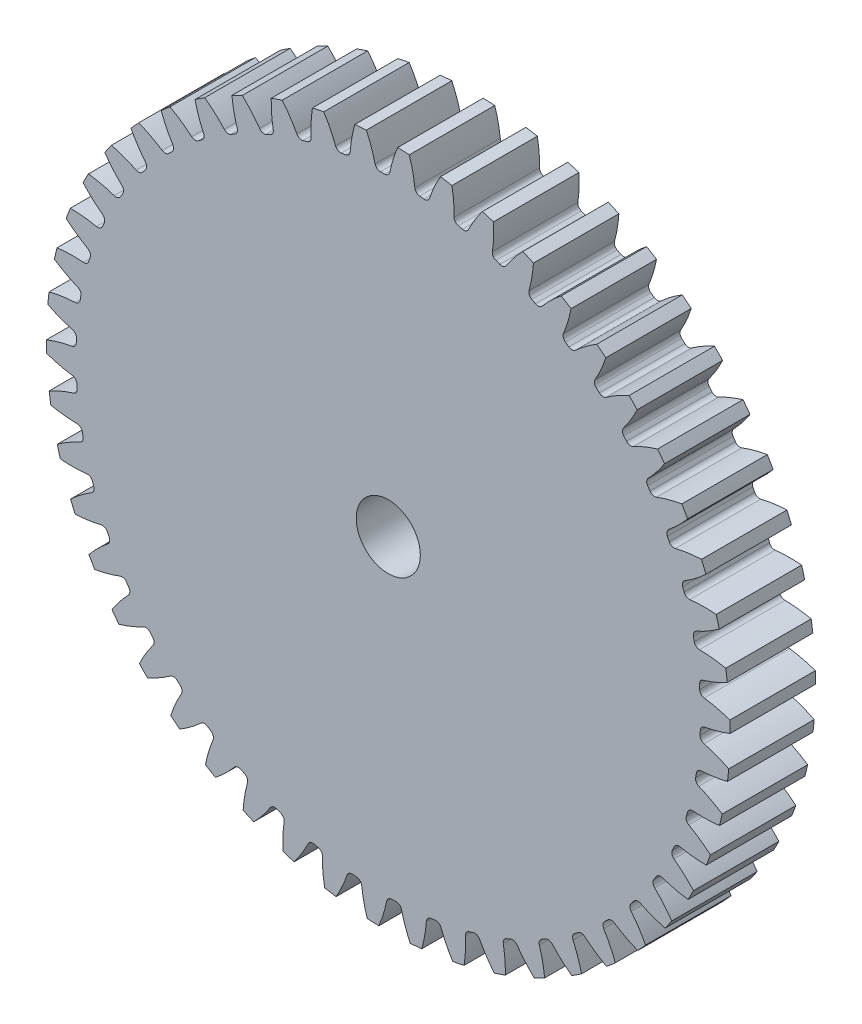
SolidWorks part; units mm, degrees
ref_plane "Front" through (0, 0, 0) normal (0, 0, 1) x (1, 0, 0)
ref_plane "Top" through (0, 0, 0) normal (0, 1, 0) x (1, 0, 0)
ref_plane "Right" through (0, 0, 0) normal (1, 0, 0) x (0, 0, -1)
sketch "Sketch3" plane through (0, 0, 0) normal (0, 0, 1) x (1, 0, 0)
  circle A0 centre (0, 0) radius 25.4
  dimension "od" = 50.8
extrude "gearBody" add sketch "Sketch3" along normal blind 6.35
sketch "Sketch2" plane through (0, 0, 0) normal (0, 0, 1) x (1, 0, 0)
  line L0 (0, 0) -> (21.8453, 9.0486) construction
  line L1 (29.4137, -6.2294) -> (0, 0) construction
  line L2 (0, 0) -> (36.3143, 0) construction
  line L3 (24.4213, -0.2936) -> (24.3506, -1.8801) construction
  line L5 (24.386, -1.0869) -> (0, 0) construction
  line L7 (0, 0) -> (23.6451, 0) construction
  arc A0 (23.6404, -0.4745) -> (23.5889, -1.6304) centre (0, 0) ccw construction
  arc A1 (25.4, 0.0332) -> (25.2963, -2.2927) centre (0, 0) ccw construction
  arc A2 (24.4213, -0.2936) -> (24.3506, -1.8801) centre (0, 0) ccw construction
  arc A3 (23.1693, -1.1922) -> (23.1835, -0.8737) centre (0, 0) ccw
  arc A4 (29.4137, -6.2294) -> (23.4627, -1.5957) centre (20.9537, -10.9561) ccw
  arc A5 (29.4137, -6.2294) -> (29.8512, 3.5881) centre (0, 0) ccw
  arc A6 (29.8512, 3.5881) -> (23.5117, -0.4979) centre (21.8453, 9.0486) cw
  arc A7 (23.1835, -0.8737) -> (23.5117, -0.4979) centre (23.5799, -0.8886) cw
  arc A8 (23.4627, -1.5957) -> (23.1693, -1.1922) centre (23.5654, -1.2126) cw
  point P6 (29.8512, 3.5881)
  point P22 (29.4137, -6.2294)
  dimension "baseDia" = 47.2903
  dimension "od" = 50.8
  dimension "pd" = 48.8462
  dimension "rd" = 46.3999
  dimension "rFillet" = 0.3966
  dimension "pointX" = 29.8512
  dimension "pointY" = 3.5881
  dimension "CTT" = 1.5865
  dimension "flankCenterAngle" = 22.5
extrude "toothCut" cut sketch "Sketch2" along normal through all
pattern_circular "CirPattern1" count 50 over 360 about axis through (0, 0, 6.35) along (0, 0, -1) of "toothCut"
ref_axis "toothSpace" through (0, 0, 0) along (0.999, -0.0445, 0)
ref_axis "Axis2" through (25.2537, -2.722, 0) along (-0.9942, 0.1072, 0)
sketch "hub1Dia" plane through (0, 0, 0) normal (0, 0, -1) x (-1, 0, 0)
  circle A0 centre (0, 0) radius 12.7
  dimension "hub1Dia" = 25.4
sketch "hub2Dia" plane through (0, 0, 6.35) normal (0, 0, 1) x (1, 0, 0)
  circle A0 centre (0, 0) radius 12.7
  dimension "hub2dia" = 25.4
sketch "boreDia" plane through (0, 0, 0) normal (0, 0, 1) x (1, 0, 0)
  circle A0 centre (0, 0) radius 2.3812
  dimension "boreDia" = 4.7625
extrude "bore" cut sketch "boreDia" against normal mid plane 25400
sketch "kwy1sketch" plane through (0, 0, 0) normal (0, 0, 1) x (1, 0, 0)
  line L0 (-6.033, 0.5227) -> (0, 0) construction
  line L1 (28.7738, 10.2545) -> (26.5813, -15.0507)
  line L2 (26.5813, -15.0507) -> (-5.0502, -12.31)
  line L3 (28.7738, 10.2545) -> (-2.8577, 12.9952)
  line L4 (-5.0502, -12.31) -> (0, 0)
  line L5 (0, 0) -> (-2.8577, 12.9952)
  line L6 (0, 0) -> (23.177, -1.033) construction
  line L7 (27.6776, -2.3981) -> (0, 0) construction
  arc A7 (23.1693, -1.1922) -> (23.1835, -0.8737) centre (0, 0) ccw construction
  point P9 (27.6776, -2.3981)
  point P13 (-1.0064, 0.0872)
  dimension "kwy1width" = 25.4
  dimension "kwy1depth" = 27.7812
  dimension "kwy1angle" = 2.4
  dimension "kwy1Depth2" = 31.75
sketch "kwy2sketch" plane through (0, 0, 0) normal (0, 0, 1) x (1, 0, 0)
  line L0 (23.177, -1.033) -> (0, 0) construction
  line L1 (0, 0) -> (-3.2033, -2.6925) construction
  line L2 (13.0951, 27.5972) -> (29.4382, 8.1534)
  line L3 (29.4382, 8.1534) -> (5.1335, -12.2755)
  line L4 (13.0951, 27.5972) -> (-11.2097, 7.1683)
  line L5 (5.1335, -12.2755) -> (0, 0)
  line L6 (0, 0) -> (-11.2097, 7.1683)
  arc A2 (23.1693, -1.1922) -> (23.1835, -0.8737) centre (0, 0) ccw construction
  point P10 (21.2667, 17.8753)
  dimension "kwy2angle" = 42.6
  dimension "kwy2Width" = 25.4
  dimension "kwy2depth" = 27.7812
  dimension "kwy2Depth2" = 31.75
sketch "kwy3sketch" plane through (0, 0, 0) normal (0, 0, 1) x (1, 0, 0)
  line L0 (23.177, -1.033) -> (0, 0) construction
  line L1 (0, 0) -> (-0.2613, -3.0161) construction
  line L2 (-10.2545, 28.7738) -> (15.0507, 26.5813)
  line L3 (15.0507, 26.5813) -> (12.31, -5.0502)
  line L4 (-10.2545, 28.7738) -> (-12.9952, -2.8577)
  line L5 (12.31, -5.0502) -> (0, 0)
  line L6 (-12.9952, -2.8577) -> (0, 0)
  point P10 (2.3981, 27.6776)
  dimension "kwy3angle" = 87.6
  dimension "kwy3depth" = 27.7812
  dimension "kwy3width" = 25.4
  dimension "kwy3Depth2" = 31.75
sketch "kwy4sketch" plane through (0, 0, 0) normal (0, 0, 1) x (1, 0, 0)
  line L0 (23.177, -1.033) -> (0, 0) construction
  line L1 (0, 0) -> (1.5231, -1.812) construction
  line L2 (-8.1534, 29.4382) -> (-27.5972, 13.0951)
  line L3 (-27.5972, 13.0951) -> (-7.1683, -11.2097)
  line L4 (-7.1683, -11.2097) -> (0, 0)
  line L5 (12.2755, 5.1335) -> (0, 0)
  line L6 (-8.1534, 29.4382) -> (12.2755, 5.1335)
  point P15 (-17.8753, 21.2667)
  dimension "kwy4angle" = 132.6
  dimension "kwy4depth" = 27.7812
  dimension "kwy4width" = 25.4
  dimension "kwy4Depth2" = 31.75
sketch "kwy5sketch" plane through (0, 0, 0) normal (0, 0, 1) x (1, 0, 0)
  line L0 (23.177, -1.033) -> (0, 0) construction
  line L1 (0, 0) -> (2.0254, -0.1755) construction
  line L2 (-26.5813, 15.0507) -> (-28.7738, -10.2545)
  line L3 (-28.7738, -10.2545) -> (2.8577, -12.9952)
  line L4 (-26.5813, 15.0507) -> (5.0502, 12.31)
  line L5 (2.8577, -12.9952) -> (0, 0)
  line L6 (5.0502, 12.31) -> (0, 0)
  point P10 (-27.6776, 2.3981)
  dimension "kwy5width" = 25.4
  dimension "kwy5depth" = 27.7812
  dimension "kwy5angle" = 177.6
  dimension "kwy5Depth2" = 31.75
sketch "kwy6sketch" plane through (0, 0, 0) normal (0, 0, 1) x (1, 0, 0)
  line L0 (23.177, -1.033) -> (0, 0) construction
  line L1 (0, 0) -> (1.555, 1.307) construction
  line L2 (-29.4382, -8.1534) -> (-13.0951, -27.5972)
  line L3 (-13.0951, -27.5972) -> (11.2097, -7.1683)
  line L4 (-29.4382, -8.1534) -> (-5.1335, 12.2755)
  line L5 (11.2097, -7.1683) -> (0, 0)
  line L6 (-5.1335, 12.2755) -> (0, 0)
  point P10 (-21.2667, -17.8753)
  dimension "kwy6angle" = 222.6
  dimension "kwy6width" = 25.4
  dimension "kwy6depth" = 27.7812
  dimension "kwy6Depth2" = 31.75
sketch "kwy7sketch" plane through (0, 0, 0) normal (0, 0, 1) x (1, 0, 0)
  line L0 (23.177, -1.033) -> (0, 0) construction
  line L1 (0, 0) -> (0.1964, 2.2673) construction
  line L2 (-15.0507, -26.5813) -> (10.2545, -28.7738)
  line L3 (-15.0507, -26.5813) -> (-12.31, 5.0502)
  line L4 (10.2545, -28.7738) -> (12.9952, 2.8577)
  line L5 (-12.31, 5.0502) -> (0, 0)
  line L6 (12.9952, 2.8577) -> (0, 0)
  point P10 (-2.3981, -27.6776)
  dimension "kwy7angle" = 87.6
  dimension "kwy7width" = 25.4
  dimension "kwy7depth" = 27.7812
  dimension "kwy7angle1" = 267.6
  dimension "kwy7Depth2" = 31.75
sketch "kwy8sketch" plane through (0, 0, 0) normal (0, 0, 1) x (1, 0, 0)
  line L0 (23.177, -1.033) -> (0, 0) construction
  line L1 (0, 0) -> (-1.3009, 1.5478) construction
  line L2 (8.1534, -29.4382) -> (27.5972, -13.0951)
  line L3 (27.5972, -13.0951) -> (7.1683, 11.2097)
  line L4 (8.1534, -29.4382) -> (-12.2755, -5.1335)
  line L5 (7.1683, 11.2097) -> (0, 0)
  line L6 (-12.2755, -5.1335) -> (0, 0)
  point P10 (17.8753, -21.2667)
  dimension "kwy8angle" = 312.6
  dimension "kwy8width" = 25.4
  dimension "kwy8depth" = 27.7812
  dimension "kwy8Depth2" = 31.75
sketch "centerLine" plane through (0, 0, 0) normal (0, 1, 0) x (1, 0, 0)
  line L0 (0, 36.4807) -> (0, -59.6309) construction
ref_plane "CB1plane" through (0, 0, 0) normal (0, 0, -1) x (-1, 0, 0)
sketch "CB1diameter" plane through (0, 0, 0) normal (0, 0, -1) x (-1, 0, 0)
  circle A0 centre (0, 0) radius 12.7
  dimension "CB1diameter" = 25.4
ref_plane "CB2plane" through (0, 0, 6.35) normal (0, 0, 1) x (1, 0, 0)
sketch "CB2diameter" plane through (0, 0, 6.35) normal (0, 0, 1) x (1, 0, 0)
  circle A0 centre (0, 0) radius 12.7
  dimension "CB2diameter" = 25.4
ref_axis "Axis1" through (0, 0, 50) along (0, 0, -1)
